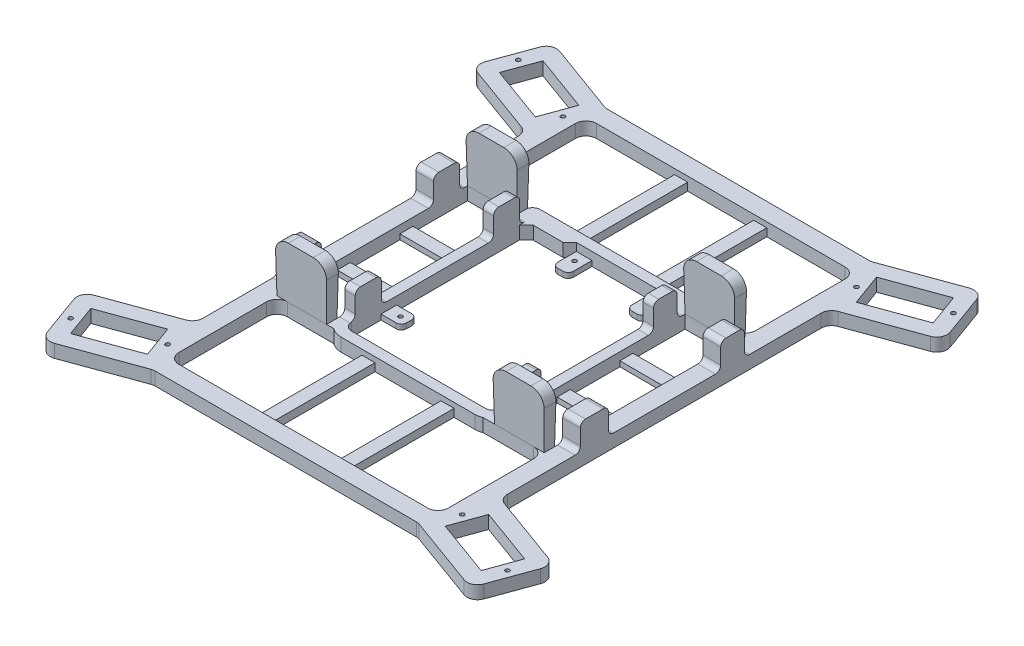
SolidWorks part; units mm, degrees
note: The reader was unsure of these and kept them because the rebuilt part matched: shared geometry of "Sketch2<3>", "Sketch2<6>", "Sketch2<7>", "Sketch2<8>", "Sketch2<11>".
ref_plane "Front Plane" through (0, 0, 0) normal (0, 0, 1) x (1, 0, 0)
ref_plane "Top Plane" through (0, 0, 0) normal (0, 1, 0) x (1, 0, 0)
ref_plane "Right Plane" through (0, 0, 0) normal (1, 0, 0) x (0, 0, -1)
sketch "Sketch2" plane through (0, 0, 0) normal (0, 1, 0) x (1, 0, 0)
  line L0 (58.0702, -62.7566) -> (90.9594, -74.7273)
  line L2 (58.0702, -62.7566) -> (49.5197, -86.249)
  line L5 (49.5197, -86.249) -> (82.4089, -98.2197)
  line L6 (90.9594, -74.7273) -> (82.4089, -98.2197)
  line L7 (-56.9139, 82.6593) -> (-78.5232, 90.5358)
  line L8 (-82.317, 98.3048) -> (-90.6656, 75.4005)
  line L9 (-61.3659, 70.4454) -> (-82.9751, 78.3219)
  line L10 (-57.7819, 63.4144) -> (-49.4333, 86.3188)
  line L11 (78.8229, -90.5294) -> (57.21, -82.6629)
  line L12 (78.8229, -90.5294) -> (83.2692, -78.3134)
  line L13 (83.2692, -78.3134) -> (61.6562, -70.4469)
  line L15 (57.21, -82.6629) -> (61.6562, -70.4469)
  line L17 (-57.7819, 63.4144) -> (-90.6656, 75.4005)
  line L18 (-61.3659, 70.4454) -> (-56.9139, 82.6593)
  line L19 (-54.5192, 88.1726) -> (-82.317, 98.3048)
  line L20 (-82.9751, 78.3219) -> (-78.5232, 90.5358)
  line L21 (49.5197, 86.249) -> (82.4089, 98.2197)
  line L22 (49.5197, 86.249) -> (58.0702, 62.7566)
  line L23 (58.0702, 62.7566) -> (90.9594, 74.7273)
  line L24 (82.4089, 98.2197) -> (90.9594, 74.7273)
  line L25 (83.2692, 78.3134) -> (61.6562, 70.4469)
  line L26 (83.2692, 78.3134) -> (78.8229, 90.5294)
  line L27 (78.8229, 90.5294) -> (57.21, 82.6629)
  line L28 (61.6562, 70.4469) -> (57.21, 82.6629)
  line L29 (-51.5059, -80) -> (-51.5059, 13.7894)
  line L30 (51.7941, 80) -> (51.7941, -80)
  line L31 (-28.5059, -15.568) -> (-28.5059, 31.432)
  line L32 (-51.5059, -80) -> (51.7941, -80)
  line L33 (-28.5059, -21.568) -> (-22.6959, -21.568)
  line L34 (-11.8458, 36.6661) -> (22.5443, 36.6661) construction
  line L35 (-32.5059, -10.3484) -> (-51.5059, -10.3484)
  line L36 (-50.641, -86.762) -> (50.9292, -86.762)
  line L37 (-90.6712, -74.7273) -> (-57.7819, -62.7566)
  line L38 (51.7941, 80) -> (-51.5059, 80)
  line L39 (58.54, 62.9277) -> (58.54, -63.2697)
  line L40 (-50.8426, 86.8325) -> (50.9292, 86.762)
  line L41 (25.7882, -35.8685) -> (-25.5051, -35.8685)
  line L42 (-28.5059, -32.9044) -> (-28.5059, -21.568)
  line L43 (-28.5059, 31.432) -> (-25.8108, 34.127)
  line L44 (-90.6712, -74.7273) -> (-82.1207, -98.2197)
  line L45 (-82.1207, -98.2197) -> (-49.2314, -86.249)
  line L46 (-57.7819, -62.7566) -> (-49.2314, -86.249)
  line L47 (-56.9217, -82.6629) -> (-78.5346, -90.5294)
  line L48 (-56.9217, -82.6629) -> (-61.368, -70.4469)
  line L49 (-61.368, -70.4469) -> (-82.9809, -78.3134)
  line L50 (-78.5346, -90.5294) -> (-82.9809, -78.3134)
  line L51 (-25.8108, 34.127) -> (-14.3849, 34.127)
  line L52 (-14.3849, 34.127) -> (-11.8458, 36.6661)
  line L53 (-5.8458, 36.6661) -> (16.5443, 36.6661)
  line L54 (22.5443, 36.6661) -> (25.0835, 34.127)
  line L55 (25.0835, 34.127) -> (25.8236, 34.127)
  line L56 (28.7941, 31.1565) -> (28.7941, -16.8435)
  line L57 (-32.5059, -32.9426) -> (-32.5059, 2.3863)
  line L58 (-28.5059, -15.568) -> (-22.6959, -15.568)
  line L59 (-20.6959, -19.568) -> (-20.6959, -17.568)
  line L60 (28.7941, -22.8435) -> (22.2297, -22.8435)
  line L61 (-28.5059, -21.568) -> (-28.5059, -15.568)
  line L62 (28.7941, -16.8435) -> (22.2297, -16.8435)
  line L63 (20.2297, -20.8435) -> (20.2297, -18.8435)
  line L64 (28.7941, -22.8435) -> (28.7941, -16.8435)
  line L65 (16.5443, 36.6661) -> (16.5443, 29.5198)
  line L66 (-54.5192, 88.1726) -> (-49.4333, 86.3188)
  line L67 (51.7941, 13.6866) -> (32.7941, 13.6866)
  line L68 (51.7941, 13.6866) -> (51.7941, 8.6866)
  line L69 (-13.5026, 40.6661) -> (24.2012, 40.6661)
  line L70 (-27.4677, 38.127) -> (-16.0417, 38.127) construction
  line L71 (26.8191, 38.0482) -> (26.8191, 38.0482)
  line L72 (32.7941, 31.1866) -> (32.7941, -32.8484)
  line L73 (25.774, -39.8685) -> (-25.5238, -39.8685)
  line L74 (18.5443, 27.5198) -> (20.5443, 27.5198)
  line L75 (22.5443, 36.6661) -> (22.5443, 29.5198)
  line L76 (16.5443, 36.6661) -> (22.5443, 36.6661)
  line L77 (-11.8458, 36.6661) -> (-11.8458, 29.5198)
  line L78 (-9.8458, 27.5198) -> (-7.8458, 27.5198)
  line L79 (-5.8458, 36.6661) -> (-5.8458, 29.5198)
  line L80 (-28.5059, -32.9044) -> (-28.5059, 31.432) construction
  line L81 (28.7941, -22.8435) -> (28.7941, -32.8626)
  line L82 (28.7941, 31.1565) -> (28.7941, -32.8626) construction
  line L83 (-11.8458, 36.6661) -> (-5.8458, 36.6661)
  line L84 (-32.5059, 33.0888) -> (-32.5059, 34.5888)
  line L85 (-32.5059, 34.5888) -> (-51.5059, 34.5888)
  line L86 (-32.5059, -32.9426) -> (-32.5059, -34.4426)
  line L87 (-51.5059, 35.7065) -> (-51.5059, 80)
  line L88 (51.7941, 8.6866) -> (32.7941, 8.6866)
  line L89 (-51.5059, 13.6866) -> (-51.5059, 8.6866)
  line L90 (51.7941, -10.3484) -> (32.7941, -10.3484)
  line L91 (51.7941, -10.3484) -> (51.7941, -15.3484)
  line L92 (-32.5059, -34.4426) -> (-51.5059, -34.4426)
  line L93 (17.7941, 40.6661) -> (17.7941, 80)
  line L94 (-32.5059, -38.4426) -> (-51.5059, -38.4426)
  line L95 (51.7941, -15.3484) -> (32.7941, -15.3484)
  line L96 (-51.5059, -10.3484) -> (-51.5059, -15.3484)
  line L97 (-32.5059, -15.3484) -> (-51.5059, -15.3484)
  line L98 (-32.5059, 8.6866) -> (-51.5059, 8.6866)
  line L99 (-32.5059, 13.6866) -> (-51.5059, 13.6866)
  line L100 (-32.5059, -38.4426) -> (-29.7164, -38.4426)
  line L101 (-58.2517, 63.5857) -> (-58.2518, -62.9277)
  line L107 (-32.5059, 38.5888) -> (-51.5059, 38.5888)
  line L108 (-28.5059, 33.0888) -> (-28.5059, 38.5888) construction
  line L109 (32.7941, 31.1866) -> (32.7941, 33.6866)
  line L110 (32.7941, -32.8484) -> (32.7941, -35.3484)
  line L111 (32.7941, 33.6866) -> (51.7941, 33.6866)
  line L112 (28.7941, -39.3484) -> (51.7941, -39.3484) construction
  line L113 (32.7941, 37.6866) -> (51.7941, 37.6866)
  line L116 (32.7941, -35.3484) -> (51.7941, -35.3484)
  line L122 (28.459, -39.3484) -> (51.7941, -39.3484)
  line L123 (28.7941, 37.6866) -> (51.7941, 37.6866) construction
  line L130 (17.7941, -80) -> (12.7941, -80)
  line L138 (17.7941, -80) -> (17.7941, -39.8685)
  line L152 (17.7941, 80) -> (12.7941, 80)
  line L155 (12.7941, -80) -> (12.7941, -39.8685)
  line L167 (-12.5059, -80) -> (-17.5059, -80)
  line L176 (-12.5059, -80) -> (-12.5059, -39.8685)
  line L177 (-12.5059, 80) -> (-17.5059, 80)
  line L179 (-17.5059, -80) -> (-17.5059, -39.8685)
  line L180 (12.7941, 40.6661) -> (12.7941, 80)
  line L184 (-13.5026, 40.6661) -> (-32.5059, 40.6661)
  line L185 (-17.5059, 40.6661) -> (-17.5059, 80)
  line L188 (-51.5059, 13.7894) -> (-51.5059, 35.7065)
  line L190 (-12.5059, 40.6661) -> (-12.5059, 80)
  line L193 (32.7941, 33.6866) -> (32.7941, 40.6661)
  line L194 (32.7941, 40.6661) -> (24.2012, 40.6661)
  line L195 (-26.849, 33.0888) -> (-32.5059, 33.0888)
  line L196 (-32.5059, 40.6661) -> (-32.5059, 33.0888)
  line L202 (-28.5059, 38.5888) -> (-51.5059, 38.5888) construction
  line L215 (-32.5059, -19.6747) -> (-32.5059, 33.0888)
  line L216 (-32.5059, -32.9426) -> (-32.5059, 33.0888) construction
  line L255 (28.7941, 31.1866) -> (28.7941, 37.6866) construction
  line L256 (28.7941, -32.8484) -> (28.7941, -39.3484) construction
  line L257 (24.2012, 40.6661) -> (26.8191, 38.0482) construction
  line L258 (-16.0417, 38.127) -> (-13.5026, 40.6661) construction
  line L259 (-32.5059, 33.0888) -> (-27.4677, 38.127) construction
  circle A0 centre (-23.9668, -18.6339) radius 0.8
  circle A1 centre (24.255, -19.9034) radius 0.8
  circle A2 centre (-9.0476, 33.1355) radius 0.8
  circle A3 centre (19.803, 32.1762) radius 0.8
  arc A4 (20.5443, 27.5198) -> (22.5443, 29.5198) centre (20.5443, 29.5198) ccw
  arc A5 (16.5443, 29.5198) -> (18.5443, 27.5198) centre (18.5443, 29.5198) ccw
  arc A6 (-11.8458, 29.5198) -> (-9.8458, 27.5198) centre (-9.8458, 29.5198) ccw
  arc A7 (-28.5059, -32.9044) -> (-25.5051, -35.8685) centre (-25.4693, -32.8313) ccw
  arc A8 (25.8236, 34.127) -> (28.7941, 31.1565) centre (25.7661, 31.099) cw
  arc A9 (25.7882, -35.8685) -> (28.7941, -32.8626) centre (25.815, -32.8894) ccw
  circle A10 centre (83.8651, -85.4474) radius 0.8
  arc A11 (25.774, -39.8685) -> (28.459, -39.3484) centre (25.815, -32.8894) ccw
  arc A12 (-29.7164, -38.4426) -> (-25.5238, -39.8685) centre (-25.4693, -32.8313) ccw
  arc A13 (-7.8458, 27.5198) -> (-5.8458, 29.5198) centre (-7.8458, 29.5198) ccw
  arc A14 (22.2297, -16.8435) -> (20.2297, -18.8435) centre (22.2297, -18.8435) ccw
  arc A15 (22.2297, -22.8435) -> (20.2297, -20.8435) centre (22.2297, -20.8435) cw
  arc A16 (-22.6959, -15.568) -> (-20.6959, -17.568) centre (-22.6959, -17.568) cw
  arc A17 (-22.6959, -21.568) -> (-20.6959, -19.568) centre (-22.6959, -19.568) ccw
  arc A18 (-32.5059, -32.9426) -> (-25.5238, -39.8685) centre (-25.4693, -32.8313) ccw construction
  arc A19 (-32.5059, -34.4426) -> (-29.7164, -38.4426) centre (-26.9713, -33.5557) ccw
  arc A20 (26.8191, 38.0482) -> (32.7941, 31.1866) centre (25.7661, 31.099) cw construction
  circle A21 centre (56.614, -75.5289) radius 0.8
  arc A22 (32.7941, -32.9303) -> (32.7941, -32.8484) centre (25.815, -32.8894) ccw
  arc A23 (25.774, -39.8685) -> (32.7941, -32.8484) centre (25.815, -32.8894) ccw construction
  arc A24 (32.7941, -35.3484) -> (28.459, -39.3484) centre (26.9044, -33.3144) cw
  circle A25 centre (-83.5769, -85.4474) radius 0.8
  circle A26 centre (-56.3258, -75.5289) radius 0.8
  circle A27 centre (-56.2061, 75.8578) radius 0.8
  circle A28 centre (-83.5663, 86.1172) radius 0.8
  circle A29 centre (83.8651, 85.4474) radius 0.8
  circle A30 centre (56.614, 75.5289) radius 0.8
  point P41 (56.614, -75.5289)
  point P42 (83.8651, -85.4474)
  point P46 (-83.5663, 86.1172)
  point P47 (-56.2061, 75.8578)
  point P53 (51.7941, -80)
  point P59 (56.614, 75.5289)
  point P60 (83.8651, 85.4474)
  point P63 (51.7941, 80)
  point P65 (0, 40)
  point P70 (0, -40)
  point P77 (-51.5059, 80)
  point P88 (-83.5769, -85.4474)
  point P89 (-56.3258, -75.5289)
  point P92 (-51.5059, -80)
  point P146 (22.5443, 27.5198)
  point P149 (16.5443, 27.5198)
  point P152 (-11.8458, 27.5198)
  point P155 (-5.8458, 27.5198)
  point P158 (20.2297, -16.8435)
  point P161 (20.2297, -22.8435)
  point P164 (-20.6959, -15.568)
  point P167 (-20.6959, -21.568)
  point P178 (58.54, 62.9277)
  point P182 (-23.9668, -18.6339)
  point P183 (24.255, -19.9034)
  point P184 (-58.2517, 63.5857)
  point P185 (58.54, -62.9277)
  point P188 (-58.2518, -62.9277)
  point P189 (-50.8426, 86.8325)
  point P190 (50.9292, 86.762)
  point P197 (-50.641, -86.762)
  point P198 (50.9292, -86.762)
  point P203 (-8.8458, 32.8661)
  point P204 (19.5443, 32.0966)
  point P370 (-67.7186, 86.5976)
  dimension "D58" = 2
  dimension "D61" = 4
  dimension "D73" = 0.5
  dimension "D65" = 6.65
  dimension "D2" = 160
  dimension "D5" = 13
  dimension "D6" = 23
  dimension "D7" = 1.5
  dimension "D8" = 4
  dimension "D9" = 6.65
  dimension "D10" = 20
  dimension "D11" = 13
  dimension "D12" = 23
  dimension "D13" = 6
  dimension "D14" = 6
  dimension "D15" = 3
  dimension "D16" = 3
  dimension "D17" = 35
  dimension "D18" = 6
  dimension "D19" = 3
  dimension "D20" = 12.5
  dimension "D21" = 12.5
  dimension "D22" = 6.65
  dimension "D23" = 20
  dimension "D24" = 13
  dimension "D25" = 23
  dimension "D26" = 6
  dimension "D27" = 6
  dimension "D28" = 3
  dimension "D29" = 35
  dimension "D30" = 6
  dimension "D31" = 6
  dimension "D32" = 35
  dimension "D33" = 6
  dimension "D34" = 3
  dimension "D35" = 12.5
  dimension "D36" = 12.5
  dimension "D37" = 4
  dimension "D38" = 2.5
  dimension "D39" = 6.65
  dimension "D40" = 20
  dimension "D41" = 20
  dimension "D42" = 47
  dimension "D43" = 6
  dimension "D44" = 48
  dimension "D45" = 2.5
  dimension "D46" = 6
  dimension "D47" = 13
  dimension "D48" = 23
  dimension "D49" = 6
  dimension "D50" = 6
  dimension "D51" = 3
  dimension "D52" = 35
  dimension "D53" = 6
  dimension "D54" = 3
  dimension "D55" = 12.5
  dimension "D56" = 12.5
  dimension "D57" = 6
  dimension "D59" = 19
  dimension "D60" = 19
  dimension "D67" = 1.5
  dimension "D68" = 34
  dimension "D69" = 34
  dimension "D70" = 5
  dimension "D71" = 5
  dimension "D72" = 5
  dimension "D62" = 20
  dimension "D63" = 5
  dimension "D64" = 5
  dimension "D74" = 0.5
  dimension "D75" = 0.5
  dimension "D76" = 0.5
  dimension "D77" = 1.5
  dimension "D78" = 1.5
  dimension "D79" = 1.5
  dimension "D80" = 1.5
  dimension "D81" = 3
  dimension "D82" = 3
  dimension "D83" = 2.9341
  dimension "D84" = 51.5
  dimension "D85" = 2.94
  dimension "D86" = 52
  dimension "D66" = 4
extrude "Boss-Extrude1" add sketch "Sketch2" along normal blind 2
extrude "Boss-Extrude2" add sketch "Sketch2<3>" along normal blind 5
sketch "Sketch2<3>" plane through (0, 0, 0) normal (0, 1, 0) x (1, 0, 0) same geometry as "Sketch2"
extrude "Boss-Extrude4" add sketch "Sketch2<6>" along normal blind 2
sketch "Sketch2<6>" plane through (0, 0, 0) normal (0, 1, 0) x (1, 0, 0) same geometry as "Sketch2"
extrude "Boss-Extrude5" add sketch "Sketch2<7>" along normal blind 5
sketch "Sketch2<7>" plane through (0, 0, 0) normal (0, 1, 0) x (1, 0, 0) same geometry as "Sketch2"
extrude "Boss-Extrude6" add sketch "Sketch2<8>" along normal up to surface (5 mm away) up to face at (-0.0593, 5, 18.4154)
sketch "Sketch2<8>" plane through (0, 0, 0) normal (0, 1, 0) x (1, 0, 0) same geometry as "Sketch2"
sketch "Sketch7" plane through (0, 5, 0) normal (0, 1, 0) x (1, 0, 0)
  line L0 (-32.5059, 38.5888) -> (-51.5059, 38.5888) construction
  line L1 (-51.5059, -38.4426) -> (-32.5059, -38.4426)
  line L2 (-51.5059, -38.4426) -> (-51.5059, -34.4426)
  line L3 (-51.5059, -34.4426) -> (-32.5059, -34.4426)
  line L4 (-32.5059, -38.4426) -> (-32.5059, -34.4426)
  line L5 (-51.5059, 34.5888) -> (-32.5059, 34.5888)
  line L6 (-51.5059, 34.5888) -> (-51.5059, 38.5888)
  line L7 (-51.5059, 38.5888) -> (-32.5059, 38.5888)
  line L8 (-32.5059, 34.5888) -> (-32.5059, 38.5888)
  line L10 (32.7941, -35.3484) -> (51.7941, -35.3484)
  line L11 (32.7941, -35.3484) -> (32.7941, -39.3484)
  line L12 (32.7941, -39.3484) -> (51.7941, -39.3484)
  line L13 (51.7941, -35.3484) -> (51.7941, -39.3484)
  line L14 (32.7941, 33.6866) -> (51.7941, 33.6866)
  line L15 (32.7941, 33.6866) -> (32.7941, 37.6866)
  line L16 (32.7941, 37.6866) -> (51.7941, 37.6866)
  line L17 (51.7941, 33.6866) -> (51.7941, 37.6866)
extrude "Boss-Extrude7" add sketch "Sketch7" along normal blind 20 draft 1 draft outward yes
fillet "Fillet6" radius 5 8 edges at (52.1432, 25, 37.3484) (32.445, 25, 37.3484) (-51.855, 25, 36.4426) (-32.1568, 25, 36.4426) (-51.855, 25, -36.5888) (-32.1568, 25, -36.5888) (32.445, 25, -35.6866) (52.1432, 25, -35.6866)
extrude "Boss-Extrude8" add sketch "Sketch2<11>" along normal blind 3
sketch "Sketch2<11>" plane through (0, 0, 0) normal (0, 1, 0) x (1, 0, 0) same geometry as "Sketch2"
fillet "Fillet16" radius 3 2 edges at (-32.5059, 2.5, -40.6661) (32.7941, 2.5, -40.6661)
fillet "Fillet17" radius 4 24 edges at (51.7941, 2.5, 80) (51.7941, 2.5, 39.3484) (51.7941, 2.5, -37.6866) (51.7941, 2.5, -80) (-51.5059, 2.5, -80) (-51.5059, 2.5, -38.5888) (-51.5059, 2.5, 38.4426) (-51.5059, 2.5, 80) (82.4089, 2.5, -98.2197) (90.9594, 2.5, -74.7273) (90.9594, 2.5, 74.7273) (82.4089, 2.5, 98.2197) (-82.1207, 2.5, 98.2197) (-90.6712, 2.5, 74.7273) (-82.317, 2.5, -98.3048) (-90.6656, 2.5, -75.4005) (58.54, 2.5, 62.9277) (58.54, 2.5, -62.9277) (-58.2518, 2.5, 62.9277) (-58.2517, 2.5, -63.5857) (-50.8426, 2.5, -86.8325) (50.9292, 2.5, -86.762) (50.9292, 2.5, 86.762) (-50.641, 2.5, 86.762)
sketch "Sketch10" plane through (0, 5, 0) normal (0, 1, 0) x (1, 0, 0)
  line L0 (-58.2517, 21.5888) -> (-58.2517, 31.5888)
  line L35 (32.7941, -32.3484) -> (32.7941, -21.4426)
  line L41 (28.7941, -32.3484) -> (28.7941, -21.4426)
  line L82 (-32.5059, -31.4426) -> (-28.5059, -31.4426)
  line L84 (51.7941, -32.2095) -> (51.7941, -21.4426)
  line L86 (58.54, -32.2095) -> (58.54, -21.4426)
  line L91 (-32.5059, -31.4426) -> (-32.5059, -21.4426)
  line L93 (-28.5059, -31.4426) -> (-28.5059, -21.4426)
  line L95 (-51.5059, -31.4426) -> (-51.5059, -21.4426)
  line L97 (-58.2517, -31.4426) -> (-58.2517, -21.4426)
  line L103 (54.7941, 30.6866) -> (55.54, 30.6866)
  line L108 (55.54, 30.6866) -> (58.54, 30.6866)
  line L109 (55.54, -32.3484) -> (55.54, 30.6866) construction
  line L110 (54.7941, -32.3484) -> (54.7941, 30.6866) construction
  line L111 (54.7941, 30.6866) -> (51.7941, 30.6866)
  line L112 (32.7941, 30.6866) -> (28.7941, 30.6866)
  line L113 (58.54, -35.3484) -> (58.54, 33.6866) construction
  line L114 (51.7941, -35.3484) -> (58.54, -35.3484) construction
  line L115 (51.7941, -35.3484) -> (51.7941, 33.6866) construction
  line L116 (32.7941, -32.3484) -> (28.7941, -32.3484)
  line L117 (51.7941, 33.6866) -> (58.54, 33.6866) construction
  line L122 (-32.5059, 31.5888) -> (-28.5059, 31.5888)
  line L123 (-51.5059, -31.4426) -> (-58.2517, -31.4426)
  line L124 (-51.5059, 21.5888) -> (-51.5059, 31.5888)
  line L125 (-32.5059, 21.5888) -> (-32.5059, 31.5888)
  line L126 (-28.5059, 21.5888) -> (-28.5059, 31.5888)
  line L127 (-51.5059, 21.5888) -> (-58.2517, 21.5888)
  line L128 (-32.5059, -21.4426) -> (-28.5059, -21.4426)
  line L129 (-28.5059, 21.5888) -> (-32.5059, 21.5888)
  line L130 (-51.5059, 31.5888) -> (-58.2517, 31.5888)
  line L131 (58.54, 21.5888) -> (51.7941, 21.5888)
  line L132 (-58.2517, -21.4426) -> (-51.5059, -21.4426)
  line L133 (58.54, -32.2095) -> (51.7941, -32.2095)
  line L134 (54.7941, -32.3484) -> (55.54, -32.3484) construction
  line L135 (28.7941, -21.4426) -> (32.7941, -21.4426)
  line L136 (28.7941, 21.5888) -> (28.7941, 30.6866)
  line L137 (32.7941, 21.5888) -> (32.7941, 30.6866)
  line L138 (51.7941, 21.5888) -> (51.7941, 30.6866)
  line L139 (58.54, 21.5888) -> (58.54, 30.6866)
  line L140 (32.7941, 21.5888) -> (28.7941, 21.5888)
  line L141 (51.7941, -21.4426) -> (58.54, -21.4426)
  line L142 (58.54, 60.1268) -> (58.54, -60.1268) construction
  line L143 (28.7941, 31.1565) -> (28.7941, -32.8626) construction
  line L144 (-28.5059, -32.9044) -> (-28.5059, 31.432) construction
  line L146 (-51.5059, -34.4426) -> (-51.5059, 34.5888) construction
  line L147 (-58.2517, 60.7862) -> (-58.2518, -60.1268) construction
  dimension "D1" = 3
  dimension "D2" = 3
  dimension "D3" = 10
  dimension "D4" = 10
extrude "Boss-Extrude9" add sketch "Sketch10" along normal blind 10
fillet "Fillet21" radius 2 16 edges at (55.1671, 5, 32.2095) (55.1671, 5, 21.4426) (55.1671, 5, -21.5888) (55.1671, 5, -30.6866) (30.7941, 5, -30.6866) (30.7941, 5, -21.5888) (30.7941, 5, 32.3484) (30.7941, 5, 21.4426) (-30.5059, 5, 21.4426) (-30.5059, 5, 31.4426) (-54.8788, 5, 31.4426) (-54.8788, 5, 21.4426) (-54.8788, 5, -21.5888) (-30.5059, 5, -21.5888) (-30.5059, 5, -31.5888) (-54.8788, 5, -31.5888)
fillet "Fillet23" radius 2 16 edges at (30.7941, 15, 21.4426) (55.1671, 15, 21.4426) (55.1671, 15, 32.2095) (30.7941, 15, 32.3484) (30.7941, 15, -30.6866) (30.7941, 15, -21.5888) (55.1671, 15, -21.5888) (55.1671, 15, -30.6866) (-30.5059, 15, 21.4426) (-30.5059, 15, 31.4426) (-54.8788, 15, 21.4426) (-54.8788, 15, 31.4426) (-30.5059, 15, -31.5888) (-30.5059, 15, -21.5888) (-54.8788, 15, -31.5888) (-54.8788, 15, -21.5888)
